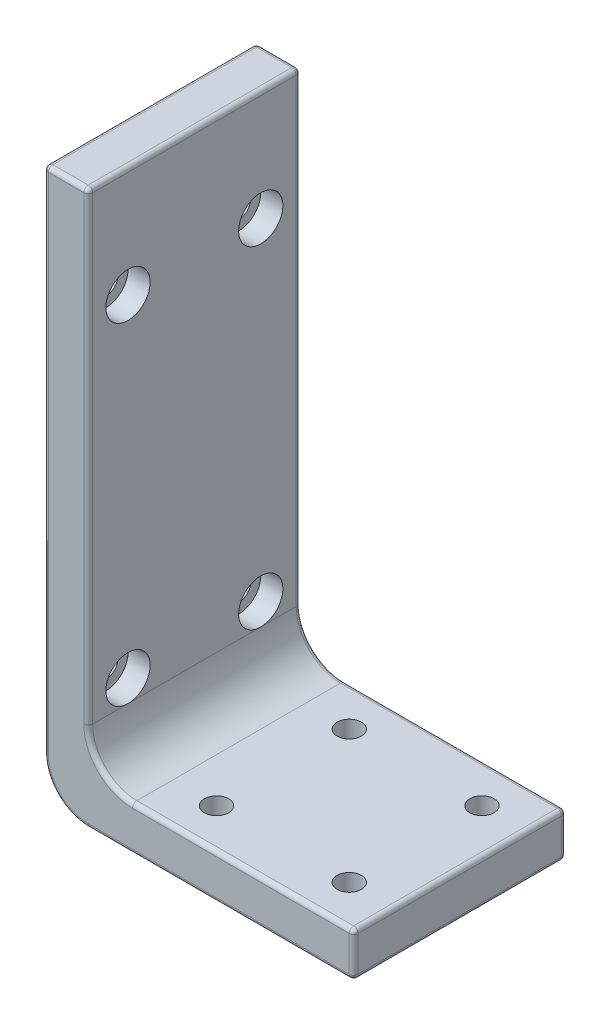
SolidWorks part; units mm, degrees
material "Nylon 101"
ref_plane "Front Plane" through (0, 0, 0) normal (0, 0, 1) x (1, 0, 0)
ref_plane "Top Plane" through (0, 0, 0) normal (0, 1, 0) x (1, 0, 0)
ref_plane "Right Plane" through (0, 0, 0) normal (1, 0, 0) x (0, 0, -1)
sketch "Sketch1" plane through (0, 0, 0) normal (0, 0, 1) x (1, 0, 0)
  line L0 (0, 125) -> (0, 0)
  line L1 (0, 0) -> (70, 0)
  line L2 (70, 0) -> (70, 10)
  line L3 (70, 10) -> (10, 10)
  line L4 (10, 10) -> (10, 125)
  line L5 (10, 125) -> (0, 125)
  dimension "D1" = 60
  dimension "D2" = 10
  dimension "D3" = 10
  dimension "D4" = 125
extrude "base" add sketch "Sketch1" along normal blind 48
fillet "root_edge_fillet" radius 10 2 edges at (0, 0, 24) (10, 10, 24)
hole_wizard "slider_bolt_hole_pattern" positions "Sketch2" profile "Sketch3" counterbore size "M5" standard "ANSI Metric" end condition through all
sketch "Sketch2" plane through (10, 0, 0) normal (1, 0, 0) x (0, 0, -1)
  line L2 (-39, 100) -> (-9, 100)
  line L3 (-39, 100) -> (-39, 25)
  line L4 (-39, 25) -> (-9, 25)
  line L5 (-9, 100) -> (-9, 25)
  line L6 (-24, 100) -> (-24, 125)
  line L7 (-48, 125) -> (0, 125) construction
  line L11 (-24, 25) -> (-24, 0)
  line L12 (-48, 0) -> (0, 0) construction
  point P58 (-39, 100)
  point P59 (-9, 25)
  point P108 (-39, 25)
  point P109 (-9, 100)
  dimension "D1" = 30
  dimension "D2" = 75
sketch "Sketch3" plane through (10, 100, 39) normal (0, 1, 0) x (0, 0, -1)
  line L0 (0, 0) -> (0, 10)
  line L1 (0, 10) -> (2.75, 10)
  line L3 (2.75, 10) -> (2.75, 5)
  line L4 (2.75, 5) -> (5, 5)
  line L5 (5, 5) -> (5, 0)
  line L7 (5, 0) -> (0, 0)
  line L11 (0, -6.35) -> (0, 107.95) construction
  dimension "Thru Hole Dia." = 5.5
  dimension "Thru Hole Depth" = 10
  dimension "C'Bore Dia." = 10
  dimension "C'Bore Depth" = 5
hole_wizard "desktop_bolt_hole_pattern" positions "Sketch4" profile "Sketch5" hole size "M5" standard "ANSI Metric" end condition through all
sketch "Sketch4" plane through (0, 10, 0) normal (0, 1, 0) x (1, 0, 0)
  line L1 (30, -9) -> (60, -9)
  line L2 (30, -9) -> (30, -39)
  line L3 (30, -39) -> (60, -39)
  line L4 (60, -9) -> (60, -39)
  line L5 (45, -9) -> (45, 0)
  line L6 (70, 0) -> (20, 0) construction
  line L8 (60, -24) -> (70, -24)
  line L9 (70, -48) -> (70, 0) construction
  point P1 (30, -9)
  point P2 (60, -39)
  point P63 (30, -39)
  point P64 (60, -9)
  dimension "D1" = 30
  dimension "D2" = 30
sketch "Sketch5" plane through (30, 10, 9) normal (1, 0, 0) x (0, 0, 1)
  line L0 (0, 0) -> (0, 10)
  line L1 (0, 10) -> (2.75, 10)
  line L2 (2.75, 10) -> (2.75, 0)
  line L5 (2.75, 0) -> (0, 0)
  line L11 (0, -6.35) -> (0, 107.95) construction
  dimension "Thru Hole Dia." = 5.5
  dimension "Thru Hole Depth" = 10
fillet "external_fillet" radius 1 20 edges at (10, 125, 24) (0, 125, 24) (70, 0, 24) (70, 10, 24) (70, 5, 0) (45, 10, 0) (12.9289, 12.9289, 0) (10, 72.5, 0) (5, 125, 0) (0, 67.5, 0) (2.9289, 2.9289, 0) (40, 0, 0) (5, 125, 48) (10, 72.5, 48) (12.9289, 12.9289, 48) (45, 10, 48) (70, 5, 48) (40, 0, 48) (2.9289, 2.9289, 48) (0, 67.5, 48)
equation "\"board_thickness\" = 18mm"
equation "\"way_width\"= 75mm"
equation "\"way_thickness\"= 50mm"
equation "\"radial_clearance\"= 0.1mm"
equation "\"slider_width\"= \"way_width\"-2* \"radial_clearance\""
equation "\"slider_thickness\" = \"way_thickness\" - 2 * \"radial_clearance\""
equation "\"column_width\"= \"way_width\" + 2 * \"board_thickness\""
equation "\"boxway_slot_width\" = 50mm"
equation "\"keeper_rail_width\" = (\"column_width\" - \"boxway_slot_width\")/2"
equation "\"slider_length\" = 125mm"
equation "\"nut_diameter\"= 22mm"
equation "\"nut_length\"= 15mm"
equation "\"leadscrew_diameter\"= 10mm"
equation "\"leadscrew_radial_clearance\"= 1mm"
equation "\"bearing_bolt_pattern_height\" = 75mm"
equation "\"bearing_bolt_pattern_width\" = 30mm"
equation "\"D1@Sketch2\"=\"bearing_bolt_pattern_width\""
equation "\"D2@Sketch2\"=\"bearing_bolt_pattern_height\""
equation "\"desktop_bolt_pattern_width\" = 30mm"
equation "\"desktop_bolt_pattern_height\" = 30mm"
equation "\"D1@Sketch4\"=\"desktop_bolt_pattern_height\""
equation "\"D2@Sketch4\"=\"desktop_bolt_pattern_width\""
equation "\"D4@Sketch1\"=\"slider_length\""
equation "\"D1@base\"=\"boxway_slot_width\" - 2mm"
